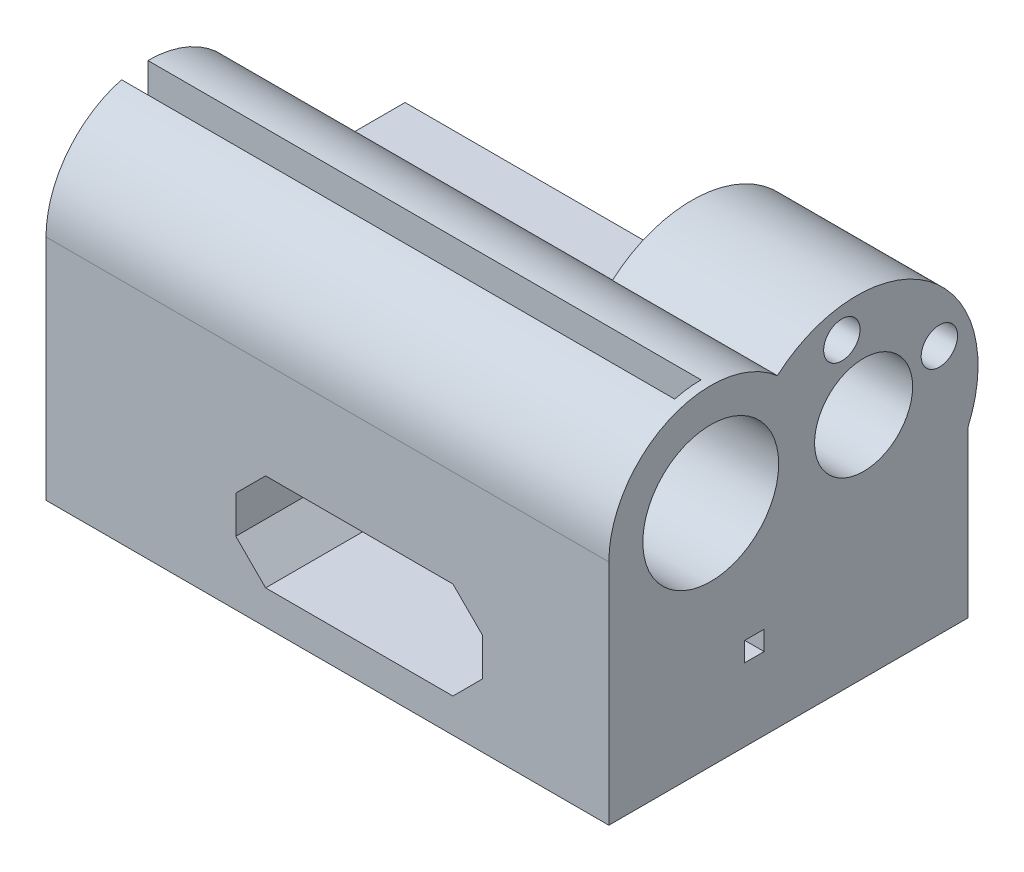
SolidWorks part; units mm, degrees
ref_plane "Front Plane" through (0, 0, 0) normal (0, 0, 1) x (1, 0, 0)
ref_plane "Top Plane" through (0, 0, 0) normal (0, 1, 0) x (1, 0, 0)
ref_plane "Right Plane" through (0, 0, 0) normal (1, 0, 0) x (0, 0, -1)
sketch "Sketch2" plane through (0, 0, 0) normal (0, 1, 0) x (1, 0, 0)
  line L1 (-29, -18.5) -> (29, -18.5)
  line L2 (-29, -18.5) -> (-29, 18.5)
  line L3 (-29, 18.5) -> (29, 18.5)
  line L4 (29, -18.5) -> (29, 18.5)
  line L5 (-29, -18.5) -> (29, 18.5) construction
  line L6 (-29, 18.5) -> (29, -18.5) construction
  point P0 (0, 0)
  dimension "D1" = 58
  dimension "D2" = 37
extrude "Boss-Extrude1" add sketch "Sketch2" along normal blind 17
sketch "Sketch3" plane through (29, 0, 0) normal (1, 0, 0) x (0, 0, -1)
  line L0 (-18.5, 0) -> (18.5, 0) construction
  line L1 (-18.5, 23.5) -> (-18.5, 17)
  line L2 (-18.5, 17) -> (-18.5, 0) construction
  line L5 (2.5, 23.5) -> (2.5, 17)
  line L6 (-18.5, 17) -> (18.5, 17) construction
  line L7 (-18.5, 17) -> (2.5, 17)
  arc A0 (2.5, 23.5) -> (-18.5, 23.5) centre (-8, 23.5) ccw
  dimension "D2" = 21
  dimension "D4" = 23.5
  dimension "D5" = 10.5
extrude "Boss-Extrude2" add sketch "Sketch3" against normal up to surface (58 mm away) up to face at (-29, 8.5, 0)
sketch "Sketch4" plane through (29, 0, 0) normal (1, 0, 0) x (0, 0, -1)
  line L1 (-18.5, 0) -> (18.5, 0) construction
  circle A0 centre (7.0436, 22) radius 12.5
  dimension "D1" = 25
  dimension "D2" = 22
extrude "Boss-Extrude3" add sketch "Sketch4" against normal blind 17
sketch "Sketch5" plane through (0, 0, -18.5) normal (0, 0, -1) x (-1, 0, 0)
  line L0 (-16, 6.57) -> (-16, 10.427)
  line L1 (-16, 10.427) -> (-12.93, 13.497)
  line L2 (-12.93, 13.497) -> (6.37, 13.497)
  line L3 (6.37, 13.497) -> (9.44, 10.427)
  line L4 (9.44, 10.427) -> (9.44, 6.57)
  line L5 (9.44, 6.57) -> (6.37, 3.5)
  line L6 (6.37, 3.5) -> (-12.93, 3.5)
  line L7 (-12.93, 3.5) -> (-16, 6.57)
  line L8 (-29, 0) -> (29, 0) construction
  line L9 (-29, 17) -> (-29, 0) construction
  dimension "D1" = 3.857
  dimension "D2" = 3.857
  dimension "D3" = 135
  dimension "D4" = 135
  dimension "D5" = 3.07
  dimension "D6" = 3.07
  dimension "D7" = 3.07
  dimension "D8" = 3.07
  dimension "D9" = 19.3
  dimension "D10" = 3.5
  dimension "D11" = 13
extrude "Cut-Extrude1" cut sketch "Sketch5" against normal through all
sketch "Sketch6" plane through (0, 0, -18.5) normal (0, 0, -1) x (-1, 0, 0)
  line L0 (-29, 0) -> (29, 0) construction
  line L1 (-29, 17) -> (-29, 0) construction
  circle A0 centre (-23, 8.5) radius 4.076
  circle A1 centre (22, 8.5) radius 4.076
  dimension "D5" = 8.152
  dimension "D6" = 8.152
  dimension "D1" = 8.5
  dimension "D2" = 8.5
  dimension "D3" = 6
  dimension "D4" = 51
extrude "Cut-Extrude2" cut sketch "Sketch6" against normal blind 23
sketch "Sketch7" plane through (29, 0, 0) normal (1, 0, 0) x (0, 0, -1)
  line L0 (-18.5, 23.5) -> (-18.5, 0) construction
  line L1 (-18.5, 0) -> (18.5, 0) construction
  circle A0 centre (-8, 23.5) radius 7
  circle A1 centre (7.7501, 23.5) radius 5.05
  dimension "D1" = 10.1
  dimension "D2" = 14
  dimension "D3" = 26.2501
  dimension "D4" = 23.5
extrude "Cut-Extrude3" cut sketch "Sketch7" against normal through all
sketch "Sketch8" plane through (29, 0, 0) normal (1, 0, 0) x (0, 0, -1)
  line L0 (7.7501, 23.5) -> (5.5097, 31.31) construction
  line L3 (7.7501, 23.5) -> (15.5601, 25.7405) construction
  line L4 (5.5097, 31.31) -> (6.0267, 29.5077) construction
  line L7 (15.5601, 25.7405) -> (13.7578, 25.2235) construction
  circle A1 centre (5.5097, 31.31) radius 1.875
  circle A2 centre (15.5601, 25.7405) radius 1.875
  dimension "D1" = 3.75
  dimension "D2" = 6.25
  dimension "D3" = 3.75
  dimension "D7" = 6.25
extrude "Cut-Extrude4" cut sketch "Sketch8" against normal through all
sketch "Sketch12" plane through (-29, 0, 0) normal (-1, 0, 0) x (0, 0, 1)
  line L0 (-18.5, 17) -> (-18.5, 0) construction
  line L1 (4.5, 7.5) -> (2.5, 7.5)
  line L2 (4.5, 7.5) -> (4.5, 9.5)
  line L3 (4.5, 9.5) -> (2.5, 9.5)
  line L4 (2.5, 7.5) -> (2.5, 9.5)
  line L5 (-18.5, 0) -> (18.5, 0) construction
  dimension "D1" = 23
  dimension "D2" = 2
  dimension "D3" = 2
  dimension "D4" = 7.5
extrude "Cut-Extrude6" cut sketch "Sketch12" against normal blind 8
mirror "Mirror1" about plane through (0, 0, 0) normal (1, 0, 0) of "Cut-Extrude6"
sketch "Sketch13" plane through (-29, 0, 0) normal (-1, 0, 0) x (0, 0, 1)
  line L0 (8, 23.5) -> (10.7176, 33.6422) construction
  line L1 (8, 23.5) -> (-2.5, 23.5) construction
  line L2 (8, 23.5) -> (8, 34) construction
  line L3 (9.8117, 30.2615) -> (10.7176, 33.6422)
  line L4 (8, 34) -> (8, 30.5)
  arc A0 (9.8117, 30.2615) -> (8, 30.5) centre (8, 23.5) ccw
  arc A1 (-2.5, 23.5) -> (8, 34) centre (8, 23.5) ccw
  arc A2 (18.5, 23.5) -> (-2.5, 23.5) centre (8, 23.5) ccw construction
  arc A3 (1.1397, 31.449) -> (-2.5, 23.5) centre (8, 23.5) ccw construction
  circle A4 centre (8, 23.5) radius 7 construction
  circle M5 centre (8, 23.5) radius 7
  arc M8 (18.5, 23.5) -> (-2.5, 23.5) centre (8, 23.5) ccw
  dimension "D1" = 15
  dimension "D2" = 90
extrude "Cut-Extrude7" cut sketch "Sketch13" against normal blind 57 contours L4 L3 M8 M5 region at (-29, 32.2657, 9.154)
sketch "Sketch14" plane through (0, 0, 0) normal (0, -1, 0) x (1, 0, 0)
  line L0 (4.558, -14.5) -> (29, -14.5) construction
  line L1 (29, 18.5) -> (29, -18.5) construction
  line L2 (4.558, -14.5) -> (4.558, -18.5) construction
  line L3 (29, -18.5) -> (-29, -18.5) construction
  circle A0 centre (4.558, -14.5) radius 1.5
  dimension "D1" = 3
  dimension "D2" = 4
  dimension "D3" = 24.442
extrude "Cut-Extrude8" cut sketch "Sketch14" against normal through all
